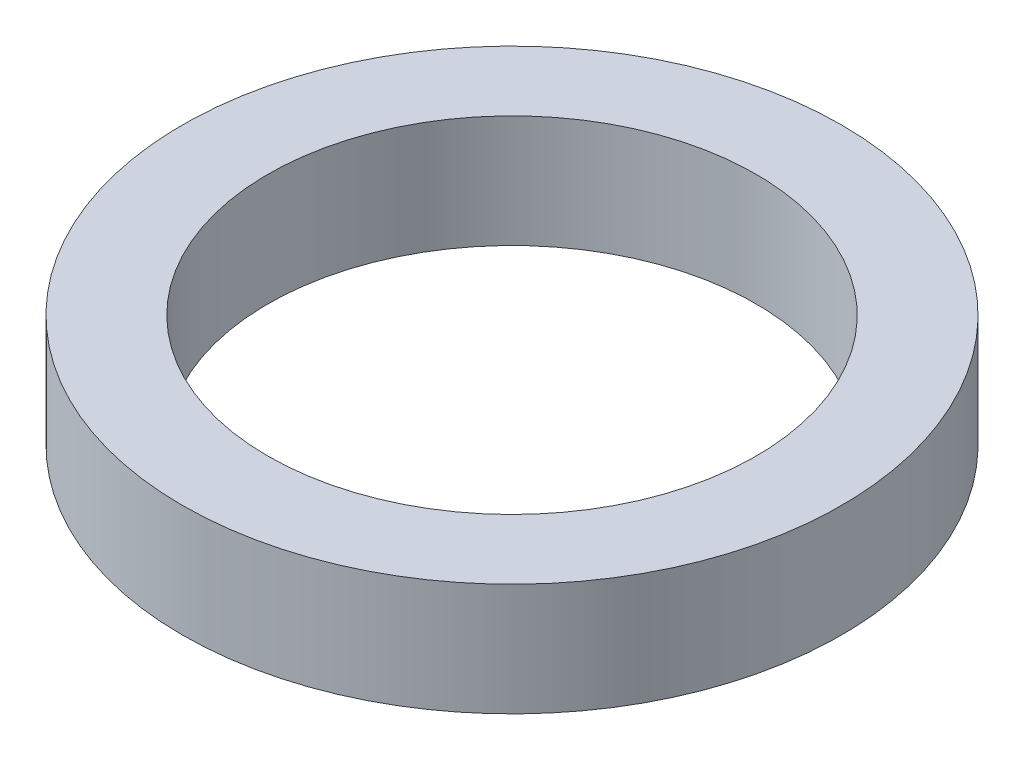
SolidWorks part; units mm, degrees
ref_plane "Front Plane" through (0, 0, 0) normal (0, 0, 1) x (1, 0, 0)
ref_plane "Top Plane" through (0, 0, 0) normal (0, 1, 0) x (1, 0, 0)
ref_plane "Right Plane" through (0, 0, 0) normal (1, 0, 0) x (0, 0, -1)
sketch "Sketch1" plane through (0, 0, 0) normal (0, 1, 0) x (1, 0, 0)
  circle A0 centre (0, 0) radius 67.5
  dimension "FLANGE_OD" = 135
extrude "Boss-Extrude1" add sketch "Sketch1" along normal blind 23
sketch "Sketch2" plane through (0, 0, 0) normal (0, 1, 0) x (1, 0, 0)
  circle A0 centre (0, 0) radius 50
  dimension "BORE_D" = 100
extrude "Cut-Extrude1" cut sketch "Sketch2" along normal through all
sketch "Sketch3" plane through (0, 23, 0) normal (0, 1, 0) x (1, 0, 0)
  circle A0 centre (0, 0) radius 30.4354 construction
  circle A1 centre (-30.4354, 0) radius 1.7957
  dimension "BOLT_D" = 3.5915
  dimension "BOLT_PCD" = 60.8707
extrude "Cut-Extrude2" cut sketch "Sketch3" against normal blind 21.4569 rebuild error yes
pattern_circular "CirPattern1" count 5 over 360 rebuild error yes
